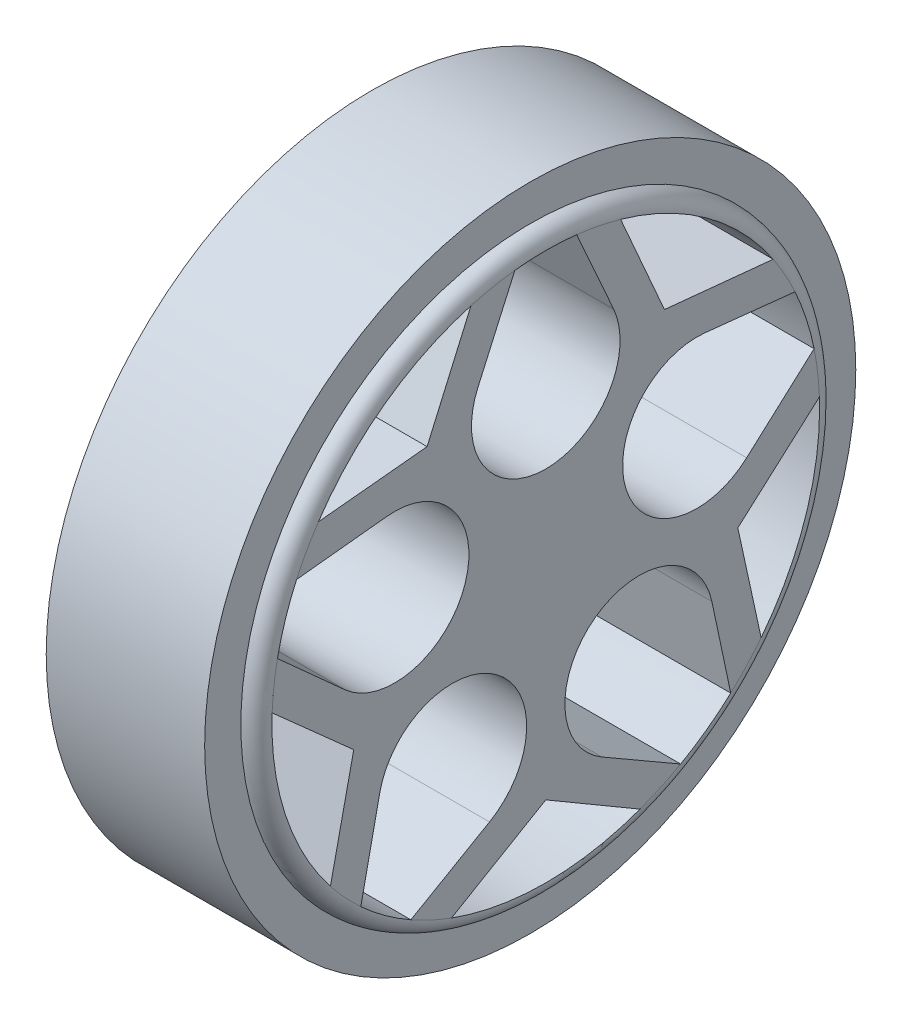
SolidWorks part; units mm, degrees
ref_plane "Front Plane" through (0, 0, 0) normal (0, 0, 1) x (1, 0, 0)
ref_plane "Top Plane" through (0, 0, 0) normal (0, 1, 0) x (1, 0, 0)
ref_plane "Right Plane" through (0, 0, 0) normal (1, 0, 0) x (0, 0, -1)
sketch "Sketch1" plane through (0, 0, 0) normal (1, 0, 0) x (0, 0, -1)
  circle A0 centre (0, 0) radius 90
  dimension "D1" = 180
extrude "Boss-Extrude1" add sketch "Sketch1" along normal blind 43.8
sketch "Sketch3" plane through (0, 0, 0) normal (-1, 0, 0) x (0, 0, 1)
  circle A0 centre (0, 0) radius 13
  point P3 (0, 0)
  dimension "D1" = 26
extrude "Boss-Extrude2" add sketch "Sketch3" along normal blind 22.5
sketch "Sketch4" plane through (-22.5, 0, 0) normal (-1, 0, 0) x (0, 0, 1)
  circle A0 centre (0, 0) radius 4
  dimension "D1" = 8
extrude "Cut-Extrude1" cut sketch "Sketch4" against normal blind 20
sketch3d "3DSketch1"
  point P0 (-11.2715, 12.9826, 0.6717)
sketch3d "3DSketch2"
  point P0 (-12.0168, 12.9145, 1.4881)
sketch "Sketch9" plane through (43.8, 0, 0) normal (1, 0, 0) x (0, 0, -1)
  circle A0 centre (0, 0) radius 80
  circle A1 centre (0, 0) radius 90 construction
  dimension "D1" = 10
extrude "Boss-Extrude3" add sketch "Sketch9" along normal blind 4.3
fillet "Fillet1" radius 4.3 1 edges at (48.1, 0, -80)
sketch "Sketch13" plane through (0, 0, 0) normal (-1, 0, 0) x (0, 0, 1)
  line L0 (0, -13) -> (0, -75.7) construction
  line L1 (0, -44.35) -> (37.289, -65.8788) construction
  line L2 (0, -44.35) -> (-37.289, -65.8788) construction
  line L3 (-12.3637, -4.0172) -> (-71.995, -23.3926) construction
  line L4 (-42.1794, -13.7049) -> (-74.1774, 15.1063) construction
  line L5 (-42.1794, -13.7049) -> (-51.1315, -55.8216) construction
  line L6 (-7.6412, 10.5172) -> (-44.4953, 61.2426) construction
  line L7 (-26.0683, 35.8799) -> (-8.5552, 75.215) construction
  line L8 (-26.0683, 35.8799) -> (-68.89, 31.3792) construction
  line L9 (7.6412, 10.5172) -> (44.4953, 61.2426) construction
  line L10 (26.0683, 35.8799) -> (68.89, 31.3792) construction
  line L11 (26.0683, 35.8799) -> (8.5552, 75.215) construction
  line L12 (12.3637, -4.0172) -> (71.995, -23.3926) construction
  line L13 (42.1794, -13.7049) -> (51.1315, -55.8216) construction
  line L14 (42.1794, -13.7049) -> (74.1774, 15.1063) construction
  line L15 (0, -55.8216) -> (26.0683, -71.0699)
  line L16 (0, -55.8216) -> (-26.0683, -71.0699)
  line L17 (-53.0895, -17.2498) -> (-59.536, -46.7542)
  line L18 (-53.0895, -17.2498) -> (-75.6471, 2.8306)
  line L19 (-32.8111, 45.1607) -> (-62.8635, 42.1742)
  line L20 (-32.8111, 45.1607) -> (-20.6842, 72.8193)
  line L21 (32.8111, 45.1607) -> (20.6842, 72.8193)
  line L22 (32.8111, 45.1607) -> (62.8635, 42.1742)
  line L23 (53.0895, -17.2498) -> (75.6471, 2.8306)
  line L24 (53.0895, -17.2498) -> (59.536, -46.7542)
  line L25 (68.89, 31.3792) -> (43.9288, 34.0027)
  line L26 (74.1774, 15.1063) -> (55.5254, -1.688)
  line L27 (37.289, -65.8788) -> (15.5529, -53.3295)
  line L28 (51.1315, -55.8216) -> (45.9132, -31.2714)
  line L29 (-51.1315, -55.8216) -> (-45.9132, -31.2714)
  line L30 (-37.289, -65.8788) -> (-15.5529, -53.3295)
  line L31 (-68.89, 31.3792) -> (-43.9288, 34.0027)
  line L32 (-74.1774, 15.1063) -> (-55.5254, -1.688)
  line L33 (8.5552, 75.215) -> (18.7637, 52.2862)
  line L34 (-8.5552, 75.215) -> (-18.7637, 52.2862)
  arc A0 (59.536, -46.7542) -> (75.6471, 2.8306) centre (0, 0) ccw
  circle A1 centre (0, 0) radius 13 construction
  circle A2 centre (0, 0) radius 13 construction
  arc A3 (-26.0683, -71.0699) -> (26.0683, -71.0699) centre (0, 0) ccw
  arc A4 (-75.6471, 2.8306) -> (-59.536, -46.7542) centre (0, 0) ccw
  arc A5 (-20.6842, 72.8193) -> (-62.8635, 42.1742) centre (0, 0) ccw
  arc A6 (62.8635, 42.1742) -> (20.6842, 72.8193) centre (0, 0) ccw
  circle A7 centre (0, 0) radius 23.3926 construction
  arc A8 (43.9288, 34.0027) -> (55.5254, -1.688) centre (41.7819, 13.5757) ccw
  arc A9 (62.8635, 42.1742) -> (20.6842, 72.8193) centre (0, 0) ccw
  arc A10 (74.1774, 15.1063) -> (68.89, 31.3792) centre (0, 0) ccw
  arc A11 (59.536, -46.7542) -> (75.6471, 2.8306) centre (0, 0) ccw
  arc A12 (37.289, -65.8788) -> (51.1315, -55.8216) centre (0, 0) ccw
  arc A13 (-26.0683, -71.0699) -> (26.0683, -71.0699) centre (0, 0) ccw
  arc A14 (-51.1315, -55.8216) -> (-37.289, -65.8788) centre (0, 0) ccw
  arc A15 (-75.6471, 2.8306) -> (-59.536, -46.7542) centre (0, 0) ccw
  arc A16 (-68.89, 31.3792) -> (-74.1774, 15.1063) centre (0, 0) ccw
  arc A17 (-20.6842, 72.8193) -> (-62.8635, 42.1742) centre (0, 0) ccw
  arc A18 (8.5552, 75.215) -> (-8.5552, 75.215) centre (0, 0) ccw
  arc A19 (45.9132, -31.2714) -> (15.5529, -53.3295) centre (25.8226, -35.5418) ccw
  arc A20 (-15.5529, -53.3295) -> (-45.9132, -31.2714) centre (-25.8226, -35.5418) ccw
  arc A21 (-55.5254, -1.688) -> (-43.9288, 34.0027) centre (-41.7819, 13.5757) ccw
  arc A22 (-18.7637, 52.2862) -> (18.7637, 52.2862) centre (0, 43.932) ccw
  point P34 (0, 0)
  point P51 (0, 0)
  point P75 (0, 0)
  dimension "D1" = 60
  dimension "D2" = 60
  dimension "D3" = 5
  dimension "D4" = 5
  dimension "D5" = 5
extrude "Cut-Extrude4" cut sketch "Sketch13" against normal blind 50 contours L32 A21 L31 A16 | L20 A5 L19 | L34 A22 L33 A18 | L22 A6 L21 | L26 A10 L25 A8 | L24 A0 L23 | L28 A19 L27 A12 | L16 A3 L15 | L30 A20 L29 A14 | L18 A4 L17 region at (0, -67.996, 0) region at (0, -21.0119, -64.6681) region at (0, 55.0099, -39.9671) region at (0, 55.0099, 39.9671) region at (0, -21.0119, 64.6681) region at (0, 14.9594, 46.0402) region at (0, -39.1642, 28.4544) region at (0, -39.1642, -28.4544) region at (0, 14.9594, -46.0402) region at (0, 48.4096, 0)
